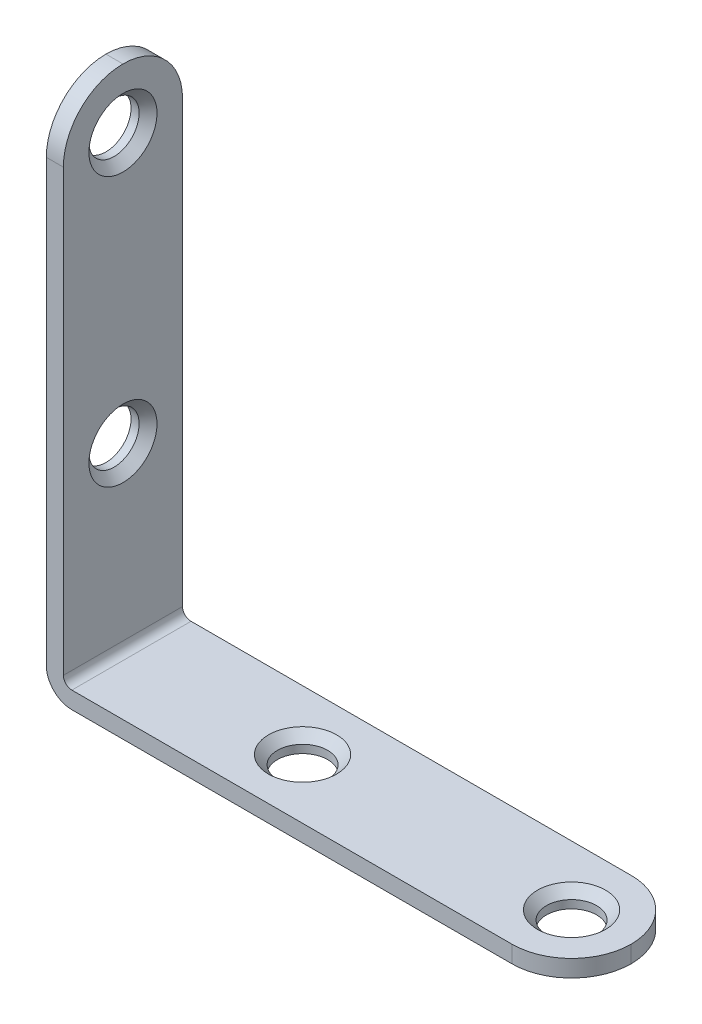
SolidWorks part; units mm, degrees
material "Acier non allié"
ref_plane "Plan de face" through (0, 0, 0) normal (0, 0, 1) x (1, 0, 0)
ref_plane "Plan de dessus" through (0, 0, 0) normal (0, 1, 0) x (1, 0, 0)
ref_plane "Plan de droite" through (0, 0, 0) normal (1, 0, 0) x (0, 0, -1)
sketch "Esquisse1" plane through (0, 0, 0) normal (0, 0, 1) x (1, 0, 0)
  line L0 (0, 3) -> (0, 61.7)
  line L1 (3, 0) -> (61.7, 0)
  line L2 (3, 2) -> (61.7, 2)
  line L3 (2, 3) -> (2, 61.7)
  line L4 (0, 61.7) -> (2, 61.7)
  line L5 (61.7, 2) -> (61.7, 0)
  arc A0 (0, 3) -> (3, 0) centre (3, 3) ccw
  arc A1 (2, 3) -> (3, 2) centre (3, 3) ccw
  point P6 (0, 0)
  dimension "D2" = 3
  dimension "D1" = 61.7
  dimension "D4" = 61.7
  dimension "D3" = 2
extrude "Boss.-Extru.1" add sketch "Esquisse1" along normal mid plane 14
fillet "Congé1" radius 7 4 edges at (1, 61.7, -7) (1, 61.7, 7) (61.7, 1, -7) (61.7, 1, 7)
hole_wizard "Fraisage pour vis à tête fraisée à 6 pans creux M51" positions "Esquisse3" profile "Esquisse2" countersink size "M5" standard "ISO" end condition through all
sketch "Esquisse3" plane through (0, 2, 0) normal (0, 1, 0) x (1, 0, 0)
  line L0 (54.7, 0) -> (23.1, 0) construction
  point P0 (54.7, 0)
  point P3 (23.1, 0)
  dimension "D1" = 31.6
sketch "Esquisse2" plane through (54.7, 2, 0) normal (1, 0, 0) x (0, 0, 1)
  line L0 (0, 0) -> (0, 2)
  line L1 (0, 2) -> (2.95, 2)
  line L2 (2.95, 2) -> (2.95, 1.05)
  line L3 (2.95, 1.05) -> (4, 0)
  line L5 (4, 0) -> (0, 0)
  line L6 (-2.95, 1.05) -> (-4, 0) construction
  line L11 (0, -6.35) -> (0, 107.95) construction
  dimension "Diamètre du perçage jusqu'au prochain" = 5.9
  dimension "Profondeur du perçage jusqu'au prochain" = 2
  dimension "Diamètre du fraisage entrant" = 8
  dimension "Angle du fraisage entrant" = 90
hole_wizard "Fraisage pour vis à tête fraisée à 6 pans creux M52" positions "Esquisse5" profile "Esquisse4" countersink size "M5" standard "ISO" end condition through all
sketch "Esquisse5" plane through (2, 0, 0) normal (1, 0, 0) x (0, 0, -1)
  line L0 (0, 54.7) -> (0, 23.1) construction
  point P0 (0, 54.7)
  point P3 (0, 23.1)
  dimension "D1" = 31.6
sketch "Esquisse4" plane through (2, 54.7, 0) normal (0, 1, 0) x (0, 0, -1)
  line L0 (0, 0) -> (0, 2)
  line L1 (0, 2) -> (2.95, 2)
  line L2 (2.95, 2) -> (2.95, 1.05)
  line L3 (2.95, 1.05) -> (4, 0)
  line L5 (4, 0) -> (0, 0)
  line L6 (-2.95, 1.05) -> (-4, 0) construction
  line L11 (0, -6.35) -> (0, 107.95) construction
  dimension "Diamètre du perçage jusqu'au prochain" = 5.9
  dimension "Profondeur du perçage jusqu'au prochain" = 2
  dimension "Diamètre du fraisage entrant" = 8
  dimension "Angle du fraisage entrant" = 90
